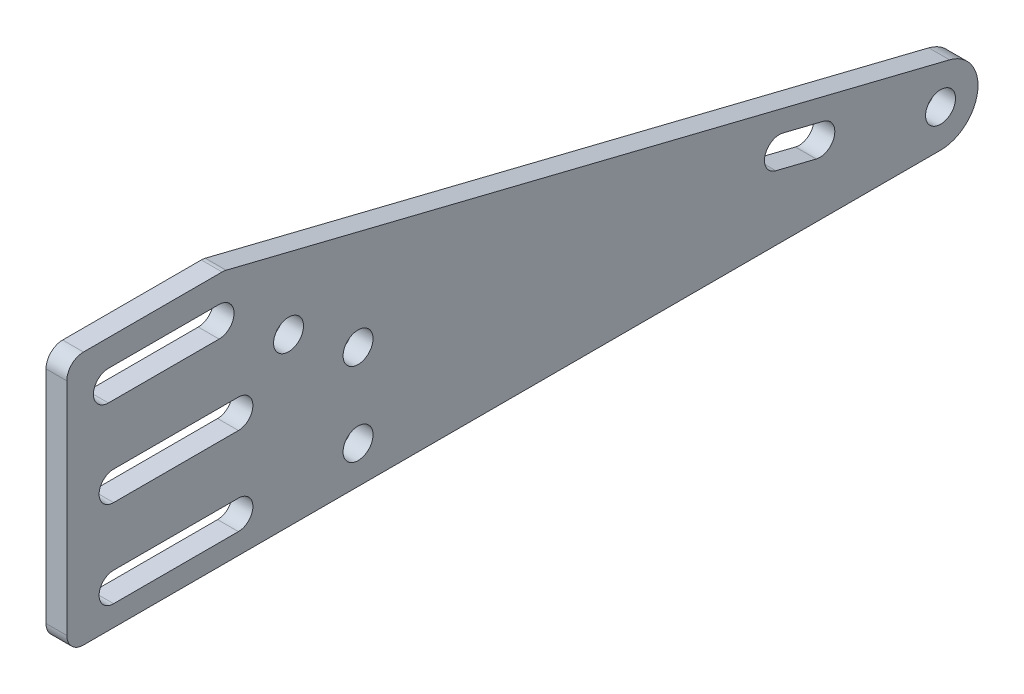
SolidWorks part; units mm, degrees
material "Acrylic (Medium-high impact)"
ref_plane "Front Plane" through (0, 0, 0) normal (0, 0, 1) x (1, 0, 0)
ref_plane "Top Plane" through (0, 0, 0) normal (0, 1, 0) x (1, 0, 0)
ref_plane "Right Plane" through (0, 0, 0) normal (1, 0, 0) x (0, 0, -1)
sketch "Sketch1" plane through (0, 0, 0) normal (1, 0, 0) x (0, 0, -1)
  line L0 (0, 6.35) -> (0, -6.35) construction
  line L1 (0, -6.35) -> (88.9, -6.35) construction
  line L2 (88.9, -6.35) -> (0, 6.35) construction
  line L3 (0, 6.35) -> (88.9, 6.35) construction
  line L4 (88.9, 6.35) -> (88.9, -6.35) construction
  line L5 (-20.1358, 26.5952) -> (90.2764, -0.8032)
  line L6 (0, -12.065) -> (88.9, -12.065)
  line L7 (-20.7475, 26.67) -> (-41.91, 26.67)
  line L8 (-44.45, 24.13) -> (-44.45, -9.525)
  line L9 (-41.91, -12.065) -> (0, -12.065)
  line L11 (0, 6.35) -> (-10.6066, 13.335) construction
  line L12 (-10.6066, 13.335) -> (-21.2132, 20.32) construction
  line L13 (-21.2132, 20.32) -> (-38.1, 20.32) construction
  circle A0 centre (0, 6.35) radius 2.286
  circle A1 centre (0, -6.35) radius 2.286
  circle A2 centre (88.9, -6.35) radius 2.286
  circle A3 centre (0, -6.35) radius 5.715 construction
  circle A4 centre (0, 6.35) radius 5.715 construction
  circle A5 centre (88.9, -6.35) radius 5.715 construction
  circle A6 centre (88.9, 6.35) radius 2.286 construction
  circle A7 centre (88.9, 6.35) radius 5.715 construction
  arc A8 (88.9, -12.065) -> (90.2764, -0.8032) centre (88.9, -6.35) ccw
  arc A9 (-20.7475, 26.67) -> (-20.1358, 26.5952) centre (-20.7475, 24.13) cw
  arc A10 (-44.45, -9.525) -> (-41.91, -12.065) centre (-41.91, -9.525) ccw
  arc A12 (-41.91, 26.67) -> (-44.45, 24.13) centre (-41.91, 24.13) ccw
  circle A13 centre (-21.2132, 20.32) radius 2.286
  circle A14 centre (-10.6066, 13.335) radius 2.286
  circle A15 centre (-38.1, 20.32) radius 2.286
  dimension "D1" = 4.572
  dimension "D4" = 11.43
  dimension "D5" = 2.54
  dimension "D7" = 6.35
  dimension "D9" = 32.385
  dimension "D11" = 6.35
  dimension "D2" = 12.7
  dimension "D3" = 88.9
  dimension "D6" = 44.45
  dimension "D8" = 6.35
  dimension "D10" = 12.7
extrude "Boss-Extrude1" add sketch "Sketch1" along normal blind 3.175
sketch "Sketch2" plane through (3.175, 0, 0) normal (1, 0, 0) x (0, 0, -1)
  line L0 (-35.1004, 12.065) -> (-44.45, 12.065) construction
  line L1 (-44.45, 24.13) -> (-44.45, -9.525) construction
  line L2 (-37.3103, 6.6801) -> (-37.3103, -6.6801) construction
  line L3 (-37.3103, 8.89) -> (-37.3103, 12.065) construction
  line L5 (-37.3103, -8.89) -> (-37.3103, -12.065) construction
  line L6 (-41.91, -12.065) -> (88.9, -12.065) construction
  line L7 (-35.1004, 12.065) -> (-35.1004, -12.065) construction
  line L8 (-39.5202, 12.065) -> (-39.5202, -12.065) construction
  line L9 (64.3105, 0.0135) -> (70.4736, -1.5158) construction
  line L10 (64.8611, 2.2322) -> (71.0241, 0.7029)
  line L11 (63.7599, -2.2052) -> (69.923, -3.7345)
  line L12 (90.2764, -0.8032) -> (-20.1358, 26.5952) construction
  circle A0 centre (-37.3103, 6.6801) radius 2.2099
  circle A1 centre (-37.3103, -6.6801) radius 2.2099
  circle A2 centre (0, -6.35) radius 2.286 construction
  arc A3 (64.8611, 2.2322) -> (63.7599, -2.2052) centre (64.3105, 0.0135) ccw
  arc A4 (69.923, -3.7345) -> (71.0241, 0.7029) centre (70.4736, -1.5158) ccw
  circle A5 centre (0, 6.35) radius 2.286 construction
  circle A6 centre (88.9, -6.35) radius 2.286 construction
  point P11 (67.392, -0.7512)
  dimension "D3" = 4.4198
  dimension "D1" = 3.175
  dimension "D2" = 35.1004
  dimension "D4" = 24.13
  dimension "D5" = 3.175
  dimension "D6" = 6.35
  dimension "D7" = 19.05
extrude "Cut-Extrude1" cut sketch "Sketch2" against normal through all
sketch "Sketch3" plane through (3.175, 0, 0) normal (1, 0, 0) x (0, 0, -1)
  line L0 (-41.275, 23.495) -> (-20.8251, 23.495) construction
  line L2 (-20.8251, 23.495) -> (88.9, -3.733) construction
  line L3 (88.9, -3.733) -> (88.9, -8.89) construction
  line L4 (88.9, -8.89) -> (-41.275, -8.89) construction
  line L5 (-41.275, -8.89) -> (-41.275, 23.495) construction
  line L6 (-44.45, 24.13) -> (-44.45, -9.525) construction
  line L9 (90.2764, -0.8032) -> (-20.1358, 26.5952) construction
  line L10 (-41.91, -12.065) -> (88.9, -12.065) construction
  line L11 (-20.7475, 26.67) -> (-41.91, 26.67) construction
  circle A0 centre (-37.3103, 6.6801) radius 5.461 construction
  circle A1 centre (-37.3103, -6.6801) radius 5.461 construction
  circle A2 centre (-10.6066, 13.335) radius 5.461 construction
  circle A3 centre (0, 6.35) radius 5.461 construction
  circle A4 centre (0, -6.35) radius 5.461 construction
  circle A5 centre (88.9, -6.35) radius 5.461 construction
  circle A6 centre (0, -6.35) radius 2.286 construction
  circle A7 centre (-21.2132, 20.32) radius 5.461 construction
  circle A8 centre (-21.2132, 20.32) radius 2.286 construction
  text T0 "6" font "Stencil" height 24.13
  point P8 (-31.3288, 26.67)
  point P14 (88.9, -6.35)
  dimension "D7" = 3.175
  dimension "D1" = 3.175
  dimension "D2" = 3.175
  dimension "D4" = 3.175
  dimension "D5" = 3.175
extrude "Cut-Extrude2" [suppressed] cut sketch "Sketch3" against normal through all
sketch "Sketch4" plane through (3.175, 0, 0) normal (1, 0, 0) x (0, 0, -1)
  line L0 (-41.275, 23.495) -> (-20.8251, 23.495) construction
  line L1 (-7.3953, 8.483) -> (-5.7259, 7.3836)
  line L2 (2.286, -0.9994) -> (2.286, 0.9994)
  line L3 (2.286, 11.7006) -> (2.286, 16.9482)
  line L4 (-2.286, 11.6673) -> (-2.286, 18.3979)
  line L5 (88.9, -3.733) -> (88.9, -8.89) construction
  line L6 (-41.275, -8.89) -> (-41.275, 23.495) construction
  line L7 (-4.8807, 12.3014) -> (-3.1835, 11.1837)
  line L8 (-13.8179, 18.187) -> (-15.4872, 19.2864)
  line L9 (-15.07, 22.0669) -> (-2.7681, 19.0142)
  line L10 (88.9, -8.89) -> (-41.275, -8.89) construction
  line L11 (88.9, -3.733) -> (88.9, -8.89) construction
  line L12 (-41.275, 14.7784) -> (-41.275, 11.7864)
  line L13 (-32.5584, 23.495) -> (-26.7548, 23.495)
  line L14 (5.6764, 7.9375) -> (36.674, 7.9375)
  line L15 (-12.9295, -8.89) -> (-5.7907, -8.89)
  line L16 (-2.286, 0.9994) -> (-2.286, -0.9994)
  line L17 (62.9952, -5.2867) -> (69.1583, -6.8161) construction
  line L18 (62.0245, -5.8577) -> (62.0245, -8.255)
  line L19 (76.7196, -0.7104) -> (83.8915, -2.4901)
  line L20 (62.6595, -8.89) -> (83.1093, -8.89)
  line L21 (62.8124, -5.2414) -> (69.1583, -6.8161)
  line L22 (20.9031, -8.89) -> (58.2145, -8.89)
  line L23 (-20.8251, 23.495) -> (88.9, -3.733) construction
  line L24 (5.6764, 4.7625) -> (46.0273, 4.7625)
  line L25 (3.0739, 17.5645) -> (36.8269, 9.1888)
  line L33 (0, 6.35) -> (5.6764, 6.35) construction
  line L34 (5.6764, 6.35) -> (5.6764, 7.9375) construction
  line L35 (5.6764, 6.35) -> (5.6764, 4.7625) construction
  line L36 (58.8495, 3.2273) -> (58.8495, -8.255)
  line L40 (5.9775, -8.8619) -> (46.2141, 3.5206)
  line L41 (58.0277, 3.8342) -> (20.7163, -7.6481)
  circle A0 centre (-37.3103, 6.6801) radius 5.461 construction
  circle A1 centre (-21.2132, 20.32) radius 5.461 construction
  arc A2 (62.0245, -5.8577) -> (62.8124, -5.2414) centre (62.6595, -5.8577) cw
  circle A4 centre (-38.1, 20.32) radius 5.461 construction
  circle A5 centre (-10.6066, 13.335) radius 5.461 construction
  circle A6 centre (88.9, -6.35) radius 5.461 construction
  arc A7 (-11.5416, 7.9546) -> (-8.0426, 8.5133) centre (-10.6066, 13.335) ccw
  circle A8 centre (-10.6066, 13.335) radius 2.286 construction
  circle A10 centre (0, -6.35) radius 5.461 construction
  circle A11 centre (0, 6.35) radius 5.461 construction
  circle A12 centre (0, 6.35) radius 2.286 construction
  arc A13 (-5.4424, 6.8009) -> (-5.7259, 7.3836) centre (-6.0752, 6.8533) ccw
  arc A14 (-40.2932, 11.2545) -> (-34.3002, 11.2366) centre (-37.3103, 6.6801) cw
  arc A15 (-26.1776, 22.5954) -> (-26.4174, 18.6651) centre (-21.2132, 20.32) ccw
  arc A16 (-26.7528, 17.8978) -> (-33.3843, 11.4781) centre (-20.7119, 5.0226) ccw
  arc A17 (-26.7548, 23.495) -> (-26.1776, 22.5954) centre (-26.7548, 22.86) cw
  arc A18 (-26.7528, 17.8978) -> (-26.4174, 18.6651) centre (-27.0225, 18.4727) ccw
  arc A19 (-33.3843, 11.4781) -> (-34.3002, 11.2366) centre (-33.9501, 11.7664) cw
  arc A20 (-41.275, 11.7864) -> (-40.2932, 11.2545) centre (-40.64, 11.7864) ccw
  arc A21 (-40.3754, 15.3556) -> (-33.1356, 22.5954) centre (-38.1, 20.32) ccw
  arc A22 (-12.2493, 7.1182) -> (-13.4861, -7.9493) centre (-29.7211, 0.9679) cw
  arc A23 (-5.4424, 6.8009) -> (-2.6167, 1.5567) centre (0, 6.35) ccw
  arc A24 (-2.6167, -1.5567) -> (-5.1875, -8.0566) centre (0, -6.35) ccw
  arc A25 (-8.0426, 8.5133) -> (-7.3953, 8.483) centre (-7.7445, 7.9527) cw
  arc A26 (2.6167, 1.5567) -> (5.0851, 4.359) centre (0, 6.35) ccw
  arc A27 (-13.4861, -7.9493) -> (-12.9295, -8.89) centre (-12.9295, -8.255) ccw
  arc A28 (-5.7907, -8.89) -> (-5.1875, -8.0566) centre (-5.7907, -8.255) ccw
  arc A29 (-2.286, -0.9994) -> (-2.6167, -1.5567) centre (-2.921, -0.9994) cw
  arc A30 (-2.6167, 1.5567) -> (-2.286, 0.9994) centre (-2.921, 0.9994) cw
  arc A31 (60.0475, 3.4267) -> (62.9952, -5.2867) centre (64.3105, 0.0135) ccw construction
  arc A32 (69.1583, -6.8161) -> (75.8377, -0.4916) centre (70.4736, -1.5158) ccw construction
  arc A33 (69.923, -3.7345) -> (71.0241, 0.7029) centre (70.4736, -1.5158) ccw construction
  arc A34 (64.8611, 2.2322) -> (63.7599, -2.2052) centre (64.3105, 0.0135) ccw construction
  arc A35 (75.9319, -1.3464) -> (69.1583, -6.8161) centre (70.4736, -1.5158) cw
  arc A36 (83.7125, -8.0566) -> (84.2762, -3.4443) centre (88.9, -6.35) cw
  arc A37 (62.0245, -8.255) -> (62.6595, -8.89) centre (62.6595, -8.255) ccw
  arc A38 (75.9319, -1.3464) -> (76.7196, -0.7104) centre (76.5666, -1.3267) cw
  arc A39 (84.2762, -3.4443) -> (83.8915, -2.4901) centre (83.7386, -3.1064) ccw
  arc A40 (83.1093, -8.89) -> (83.7125, -8.0566) centre (83.1093, -8.255) ccw
  arc A43 (5.1875, -8.0566) -> (2.6167, -1.5567) centre (0, -6.35) ccw
  arc A45 (2.6167, 11.1433) -> (2.286, 11.7006) centre (2.921, 11.7006) cw
  arc A48 (20.9031, -8.89) -> (20.7163, -7.6481) centre (20.9031, -8.255) cw
  arc A49 (3.0739, 17.5645) -> (2.286, 16.9482) centre (2.921, 16.9482) ccw
  arc A50 (2.286, 0.9994) -> (2.6167, 1.5567) centre (2.921, 0.9994) cw
  arc A52 (2.6167, -1.5567) -> (2.286, -0.9994) centre (2.921, -0.9994) cw
  arc A53 (-15.7708, 19.8691) -> (-15.8469, 21.3328) centre (-21.2132, 20.32) ccw
  arc A55 (-5.1642, 12.8841) -> (-13.1705, 18.1567) centre (-10.6066, 13.335) ccw
  arc A56 (-11.5416, 7.9546) -> (-12.2493, 7.1182) centre (-11.6503, 7.329) ccw
  arc A59 (-40.3754, 15.3556) -> (-41.275, 14.7784) centre (-40.64, 14.7784) ccw
  arc A60 (-33.1356, 22.5954) -> (-32.5584, 23.495) centre (-32.5584, 22.86) cw
  circle A61 centre (-38.1, 20.32) radius 2.286 construction
  arc A62 (-4.8807, 12.3014) -> (-5.1642, 12.8841) centre (-4.5314, 12.8317) cw
  arc A63 (-2.286, 18.3979) -> (-2.7681, 19.0142) centre (-2.921, 18.3979) ccw
  arc A64 (-15.8469, 21.3328) -> (-15.07, 22.0669) centre (-15.2229, 21.4506) cw
  arc A65 (-13.1705, 18.1567) -> (-13.8179, 18.187) centre (-13.4687, 18.7173) cw
  arc A66 (-15.4872, 19.2864) -> (-15.7708, 19.8691) centre (-15.138, 19.8167) cw
  arc A67 (-3.1835, 11.1837) -> (-2.286, 11.6673) centre (-2.865, 11.6673) ccw
  arc A68 (5.0851, 8.341) -> (2.6167, 11.1433) centre (0, 6.35) ccw
  arc A69 (5.6764, 4.7625) -> (5.0851, 4.359) centre (5.6764, 4.1275) ccw
  arc A71 (36.674, 7.9375) -> (36.8269, 9.1888) centre (36.674, 8.5725) ccw
  arc A72 (5.6764, 7.9375) -> (5.0851, 8.341) centre (5.6764, 8.5725) cw
  arc A75 (58.8495, -8.255) -> (58.2145, -8.89) centre (58.2145, -8.255) cw
  arc A76 (5.1875, -8.0566) -> (5.9775, -8.8619) centre (5.7907, -8.255) ccw
  arc A77 (46.0273, 4.7625) -> (46.2141, 3.5206) centre (46.0273, 4.1275) cw
  arc A78 (58.8495, 3.2273) -> (58.0277, 3.8342) centre (58.2145, 3.2273) ccw
  point P36 (-25.6564, 23.495)
  point P39 (-26.2182, 18.1354)
  point P42 (-33.7126, 10.7885)
  point P45 (-41.275, 10.4356)
  point P66 (-4.8343, -8.89)
  point P69 (-2.286, -1.3905)
  point P72 (-2.286, 1.3905)
  point P92 (-5.3993, 7.1685)
  point P126 (60.0475, 3.4267)
  point P131 (2.286, 17.76)
  point P134 (2.286, 1.3905)
  point P139 (2.286, -1.3905)
  point P175 (-5.2073, 12.5165)
  point P178 (-2.286, 18.8946)
  point P181 (-16.1361, 22.3314)
  point P184 (-13.4913, 17.9719)
  point P187 (-15.8139, 19.5015)
  point P202 (5.2252, 7.9375)
  dimension "D1" = 3.175
  dimension "D2" = 0.635
  dimension "D4" = 3.175
  dimension "D6" = 3.175
  dimension "D3" = 3.175
extrude "Cut-Extrude3" [suppressed] cut sketch "Sketch4" against normal through all
sketch "Sketch5" plane through (3.175, 0, 0) normal (1, 0, 0) x (0, 0, -1)
  line L0 (-21.2132, 20.32) -> (-38.1, 20.32) construction
  line L1 (-21.2132, 18.034) -> (-38.1, 18.034)
  line L2 (-21.2132, 22.606) -> (-38.1, 22.606)
  line L3 (-18.2603, 6.6801) -> (-37.3103, 6.6801) construction
  line L4 (-18.2603, 4.4702) -> (-37.3103, 4.4702)
  line L5 (-18.2603, 8.89) -> (-37.3103, 8.89)
  line L6 (-18.2603, -6.6801) -> (-37.3103, -6.6801) construction
  line L7 (-18.2603, -8.89) -> (-37.3103, -8.89)
  line L8 (-18.2603, -4.4702) -> (-37.3103, -4.4702)
  line L9 (-20.7475, 26.67) -> (-41.91, 26.67) construction
  line L10 (-18.2603, 6.6801) -> (-18.2603, -6.6801) construction
  arc A0 (-21.2132, 18.034) -> (-21.2132, 22.606) centre (-21.2132, 20.32) ccw
  arc A1 (-38.1, 22.606) -> (-38.1, 18.034) centre (-38.1, 20.32) ccw
  arc A2 (-18.2603, 4.4702) -> (-18.2603, 8.89) centre (-18.2603, 6.6801) ccw
  arc A3 (-37.3103, 8.89) -> (-37.3103, 4.4702) centre (-37.3103, 6.6801) ccw
  arc A4 (-18.2603, -8.89) -> (-18.2603, -4.4702) centre (-18.2603, -6.6801) ccw
  arc A5 (-37.3103, -4.4702) -> (-37.3103, -8.89) centre (-37.3103, -6.6801) ccw
  circle A6 centre (-37.3103, -6.6801) radius 2.2099 construction
  circle A7 centre (-37.3103, 6.6801) radius 2.2099 construction
  circle A8 centre (-38.1, 20.32) radius 2.286 construction
  circle A9 centre (-21.2132, 20.32) radius 2.286 construction
  point P3 (-29.6566, 20.32)
  point P8 (-27.7853, 6.6801)
  point P16 (-27.7853, -6.6801)
  dimension "D1" = 19.05
extrude "Cut-Extrude4" cut sketch "Sketch5" against normal through all
